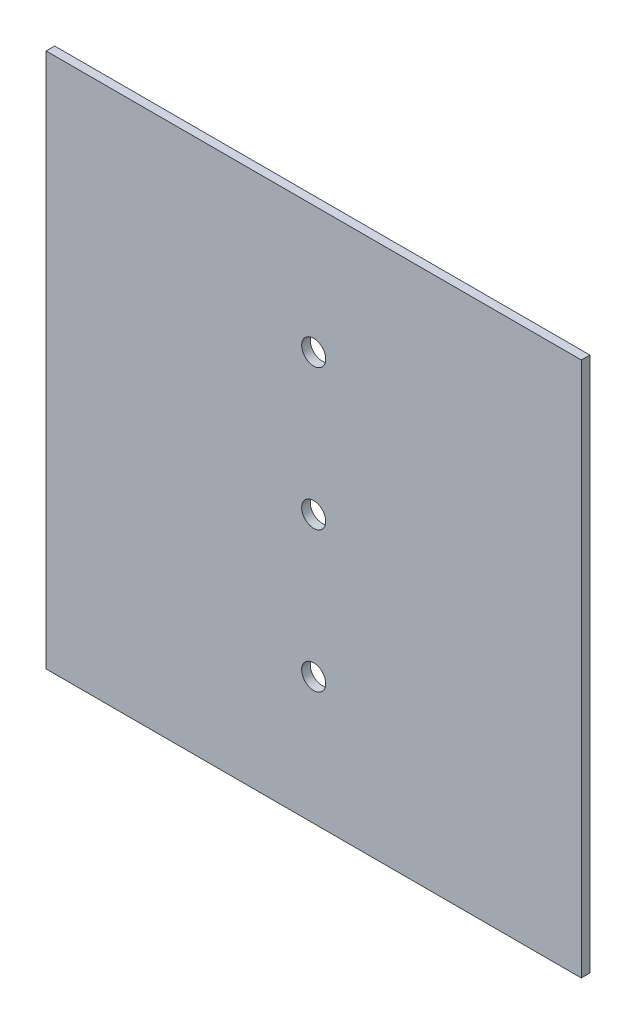
SolidWorks part; units mm, degrees
material "Copper"
ref_plane "Front Plane" through (0, 0, 0) normal (0, 0, 1) x (1, 0, 0)
ref_plane "Top Plane" through (0, 0, 0) normal (0, 1, 0) x (1, 0, 0)
ref_plane "Right Plane" through (0, 0, 0) normal (1, 0, 0) x (0, 0, -1)
sketch "Sketch1" plane through (0, 0, 0) normal (0, 0, 1) x (1, 0, 0)
  line L1 (-50, -50) -> (50, -50)
  line L2 (-50, -50) -> (-50, 50)
  line L3 (-50, 50) -> (50, 50)
  line L4 (50, -50) -> (50, 50)
  line L5 (-50, -50) -> (50, 50) construction
  line L6 (-50, 50) -> (50, -50) construction
  dimension "D1" = 100
extrude "Boss-Extrude1" add sketch "Sketch1" along normal blind 1.6
sketch "Sketch2" [suppressed] plane through (0, 0, 1.6) normal (0, 0, 1) x (1, 0, 0)
  circle A0 centre (0, 0) radius 50
  line M2 (50, -50) -> (50, 50)
  line M3 (50, 50) -> (-50, 50)
  line M4 (-50, 50) -> (-50, -50)
  line M5 (-50, -50) -> (50, -50)
  dimension "D1" = 100
extrude "Cut-Extrude1" [suppressed] cut sketch "Sketch2" against normal blind 1.6 contours A0 M3 M4 | A0 M4 M5 | A0 M5 M2 | A0 M2 M3
sketch "Sketch3" plane through (0, 0, 0) normal (0, 0, -1) x (-1, 0, 0)
  circle A0 centre (0, -26.25) radius 2.2479 construction
  circle A2 centre (0, -26.25) radius 2.2479
  circle A3 centre (0, 0) radius 2.2479
  circle A8 centre (0, 26.25) radius 2.2479 construction
  circle A9 centre (0, 26.25) radius 2.2479
  dimension "D1" = 4.4958
extrude "Cut-Extrude2" cut sketch "Sketch3" against normal up to surface (1.6 mm away) up to face at (0, 0, 1.6)
